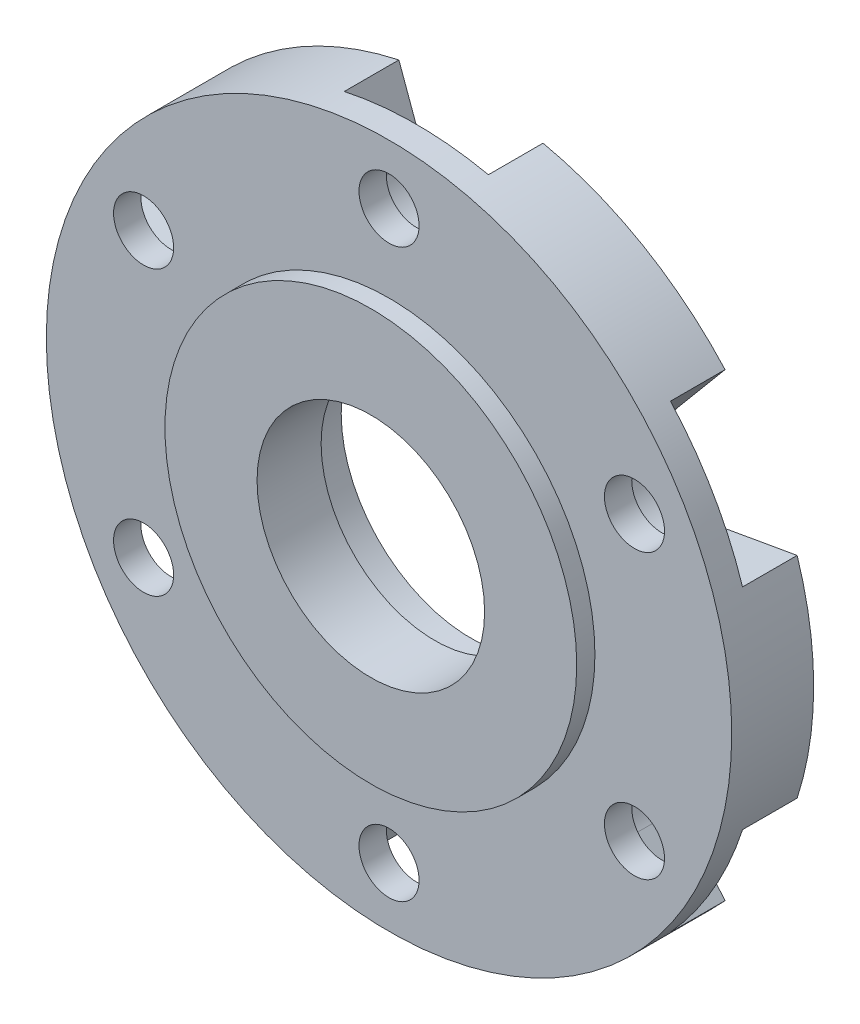
SolidWorks part; units mm, degrees
material "6061-T6 (SS)"
ref_plane "Front Plane" through (0, 0, 0) normal (0, 0, 1) x (1, 0, 0)
ref_plane "Top Plane" through (0, 0, 0) normal (0, 1, 0) x (1, 0, 0)
ref_plane "Right Plane" through (0, 0, 0) normal (1, 0, 0) x (0, 0, -1)
sketch "Sketch Spindle Skeleton" plane through (0, 0, 0) normal (1, 0, 0) x (0, 0, -1)
  line L0 (-103, -9.5) -> (-149, -9.5)
  line L5 (-1000, 0) -> (49000, 0)
  line L6 (0, -9.5) -> (0, 9.5)
  line L13 (0, 9.5) -> (-46.4, 9.5)
  line L26 (-46.4, 9.5) -> (-46.4, 14)
  line L27 (-46.4, 14) -> (-103, 14)
  line L32 (-103, 14) -> (-103, 9.5)
  line L34 (-165, 7) -> (-165, -7)
  line L36 (-103, -9.5) -> (-103, -14)
  line L37 (-103, -14) -> (-46.4, -14)
  line L38 (-46.4, -14) -> (-46.4, -9.5)
  line L39 (0, -9.5) -> (-46.4, -9.5)
  line L40 (-24.625, 37.6491) -> (-15.625, 37.6491)
  line L41 (-119.6, 22.6187) -> (-103, 22.6187)
  line L42 (-119.6, 22.6187) -> (-119.6, -22.6187)
  line L43 (-119.6, -22.6187) -> (-103, -22.6187)
  line L44 (-103, 22.6187) -> (-103, -22.6187)
  line L45 (-119.6, 22.6187) -> (-103, -22.6187) construction
  line L46 (-119.6, -22.6187) -> (-103, 22.6187) construction
  line L47 (-29.8, 22.6187) -> (-46.4, 22.6187)
  line L48 (-29.8, 22.6187) -> (-29.8, -22.6187)
  line L49 (-29.8, -22.6187) -> (-46.4, -22.6187)
  line L50 (-46.4, 22.6187) -> (-46.4, -22.6187)
  line L51 (-29.8, 22.6187) -> (-46.4, -22.6187) construction
  line L52 (-29.8, -22.6187) -> (-46.4, 22.6187) construction
  line L59 (-15.625, 37.6491) -> (-15.625, -37.6491)
  line L60 (-15.625, -37.6491) -> (-24.625, -37.6491)
  line L61 (-24.625, -22.6187) -> (-26.625, -22.6187)
  line L62 (-26.625, -22.6187) -> (-26.625, -12.5)
  line L63 (-26.625, -12.5) -> (-24.625, -12.5)
  line L64 (-24.625, -12.5) -> (-24.625, 12.5)
  line L65 (-24.625, 12.5) -> (-26.625, 12.5)
  line L66 (-26.625, 12.5) -> (-26.625, 22.6187)
  line L67 (-26.625, 22.6187) -> (-24.625, 22.6187)
  line L68 (-24.625, 22.6187) -> (-24.625, 37.6491)
  line L69 (-24.625, -22.6187) -> (-24.625, -37.6491)
  line L71 (-131.284, 37.6491) -> (-25.625, 37.6491)
  line L72 (-131.284, 37.6491) -> (-131.284, -37.6491)
  line L73 (-131.284, -37.6491) -> (-25.625, -37.6491)
  line L74 (-25.625, 37.6491) -> (-25.625, -37.6491)
  line L75 (-131.284, 37.6491) -> (-25.625, -37.6491) construction
  line L76 (-131.284, -37.6491) -> (-25.625, 37.6491) construction
  line L77 (-149, -9.5) -> (-149, -7)
  line L78 (-149, -7) -> (-165, -7)
  line L79 (-103, 9.5) -> (-149, 9.5)
  line L80 (-149, 7) -> (-165, 7)
  line L81 (-149, 9.5) -> (-149, 7)
  line L82 (-126, 9.5) -> (-126, -9.5) construction
  line L83 (-23.2, 9.5) -> (-23.2, -9.5) construction
  line L96 (-131.284, 37.6491) -> (-140.284, 37.6491)
  line L98 (-131.284, -37.6491) -> (-140.284, -37.6491)
  line L99 (-140.284, 37.6491) -> (-140.284, -37.6491)
  line L110 (-131.284, 37.6491) -> (-131.284, -37.6491)
  point P3 (0, 0)
  point P18 (-111.3, 0)
  point P24 (-38.1, 0)
  point P29 (-78.4545, 0)
  point P48 (-15.625, 31.1339)
  point P70 (-140.284, 31.1339)
revolve "Main Revolve" add sketch "Sketch Spindle Skeleton" angle 360 about L5 region at (0, 23.3435, 20.317) region at (0, 17.5594, 26.125)
sketch "Sketch Center Cut" plane through (0, 0, 24.625) normal (0, 0, 1) x (1, 0, 0)
  circle A3 centre (0, 0) radius 12.5
  dimension "D1" = 25
extrude "Cut Center" cut sketch "Sketch Center Cut" against normal through all both and the other way through all
hole_wizard "CBORE for M6 SHCS1" positions "Hole wizard sketch 1" profile "Hole wizard sketch 2" counterbore size "M6" standard "ANSI Metric" end condition through all
sketch "Hole wizard sketch 1" plane through (0, 0, 15.625) normal (0, 0, -1) x (-1, 0, 0)
  point P0 (0, 31.1339)
sketch "Hole wizard sketch 2" plane through (0, 31.1339, 15.625) normal (1, 0, 0) x (0, 1, 0)
  line L0 (0, 0) -> (0, 11)
  line L1 (0, 11) -> (3.3, 11)
  line L3 (3.3, 11) -> (3.3, 6)
  line L4 (3.3, 6) -> (5.5, 6)
  line L5 (5.5, 6) -> (5.5, 0)
  line L7 (5.5, 0) -> (0, 0)
  line L11 (0, -6.35) -> (0, 107.95) construction
  dimension "Thru Hole Dia." = 6.6
  dimension "Thru Hole Depth" = 11
  dimension "C'Bore Dia." = 11
  dimension "C'Bore Depth" = 6
pattern_circular "CirPattern1" count 6 over 360 about axis through (0, 0, 15.625) along (0, 0, 1) of "CBORE for M6 SHCS1"
sketch "Sketch1" plane through (0, 0, 15.625) normal (0, 0, -1) x (-1, 0, 0)
  circle A0 centre (0, 0) radius 14.2558
  dimension "D1" = 28.5115
extrude "Cut-Extrude1" cut sketch "Sketch1" against normal blind 3.9624
sketch "Sketch2" plane through (0, 0, 15.625) normal (0, 0, -1) x (-1, 0, 0)
  line L0 (-5.1683, 29.2528) -> (-7.9179, 36.8071)
  line L1 (0, 31.1339) -> (0, 37.65) construction
  line L2 (5.1683, 29.2528) -> (7.9179, 36.8071)
  circle A0 centre (0, 31.1339) radius 5.5 construction
  circle A1 centre (0, 0) radius 37.6491 construction
  arc A2 (-5.1683, 29.2528) -> (5.1683, 29.2528) centre (0, 31.1339) ccw
  point P37 (0.065, 0.0375)
  circle M8 centre (0, 31.1339) radius 5.5
  circle M9 centre (0, 0) radius 37.6491
  dimension "D1" = 20
extrude "Cut-Extrude2" cut sketch "Sketch2" against normal up to surface (6 mm away) contours L1 L2 M8 M9 | L1 L0 M8 M9 region at (4.7304, 35.5149, 15.625) region at (-4.7304, 35.5149, 15.625) up to face at (23.6628, -15.567, 21.625)
pattern_circular "CirPattern2" count 6 over 360 about axis through (0, 0, 1000) along (0, 0, 1) of "Cut-Extrude2" reverse direction yes
